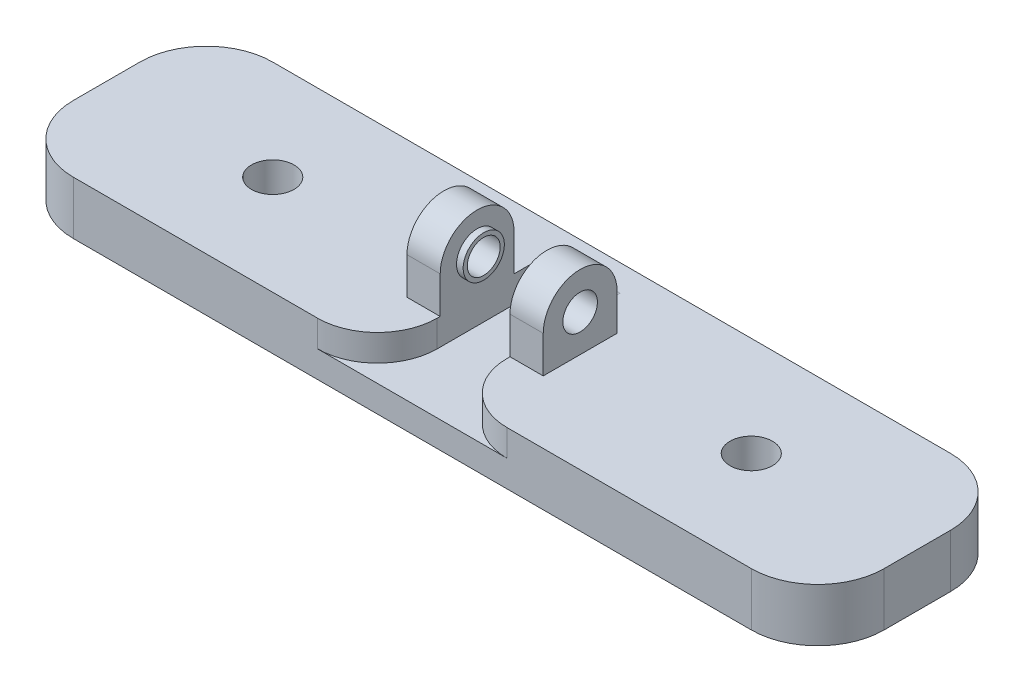
SolidWorks part; units mm, degrees
ref_plane "Front Plane" through (0, 0, 0) normal (0, 0, 1) x (1, 0, 0)
ref_plane "Top Plane" through (0, 0, 0) normal (0, 1, 0) x (1, 0, 0)
ref_plane "Right Plane" through (0, 0, 0) normal (1, 0, 0) x (0, 0, -1)
sketch "Sketch1" plane through (0, 0, 0) normal (0, 1, 0) x (1, 0, 0)
  line L1 (-61, 15) -> (61, 15)
  line L2 (-61, 15) -> (-61, -15)
  line L3 (-61, -15) -> (61, -15)
  line L4 (61, 15) -> (61, -15)
  line L5 (-61, 15) -> (61, -15) construction
  line L6 (-61, -15) -> (61, 15) construction
  point P0 (0, 0)
  dimension "D1" = 122
  dimension "D2" = 30
extrude "Boss-Extrude1" add sketch "Sketch1" along normal blind 8
ref_plane "Plane1" through (0, 0, 0) normal (1, 0, 0) x (0, 0, -1)
ref_plane "Plane2" through (5.25, 0, 0) normal (1, 0, 0) x (0, 0, -1)
ref_plane "Plane3" through (-5.25, 0, 0) normal (1, 0, 0) x (0, 0, -1)
sketch "Sketch2" plane through (5.25, 0, 0) normal (1, 0, 0) x (0, 0, -1)
  line L0 (0, 8) -> (0, 13.5522) construction
  line L1 (-15, 8) -> (15, 8) construction
  line L2 (-5.5522, 13.5522) -> (-5.5522, 8)
  line L3 (-5.5522, 8) -> (5.5522, 8)
  line L4 (5.5522, 8) -> (5.5522, 13.5522)
  circle A0 centre (0, 13.5522) radius 2.6
  arc A1 (5.5522, 13.5522) -> (-5.5522, 13.5522) centre (0, 13.5522) ccw
  dimension "D1" = 5.5522
  dimension "D2" = 5.2
  dimension "D3" = 5.5522
extrude "Boss-Extrude2" add sketch "Sketch2" along normal blind 5
sketch "Sketch3" plane through (-5.25, 0, 0) normal (1, 0, 0) x (0, 0, -1)
  line L0 (-5.5522, 13.5522) -> (-5.5522, 8)
  line L1 (-15, 8) -> (15, 8) construction
  line L2 (-5.5522, 8) -> (5.5522, 8) construction
  line L3 (-5.5522, 8) -> (5.5522, 8)
  line L4 (5.5522, 8) -> (5.5522, 13.5522)
  circle A0 centre (0, 13.5522) radius 2.475
  arc A1 (5.5522, 13.5522) -> (-5.5522, 13.5522) centre (0, 13.5522) ccw
  dimension "D1" = 4.95
extrude "Boss-Extrude3" add sketch "Sketch3" against normal blind 5
sketch "Sketch4" plane through (0, 8, 0) normal (0, 1, 0) x (1, 0, 0)
  line L0 (-61, -15) -> (61, -15) construction
  line L1 (-5.25, 9) -> (5.25, 9)
  line L2 (-5.25, 9) -> (-5.25, -15)
  line L3 (-5.25, -15) -> (5.25, -15)
  line L4 (5.25, 9) -> (5.25, -15)
  point P0 (-5.25, 5.5522)
  point P1 (5.25, -5.5522)
  point P8 (-4.25, 5.3855)
  point P9 (0, 0)
  point P10 (4.25, -15)
  point P13 (0, 0)
  dimension "D1" = 24
extrude "Cut-Extrude1" cut sketch "Sketch4" against normal blind 4
sketch "Sketch6" plane through (5.25, 0, 0) normal (-1, 0, 0) x (0, 0, 1)
  circle A0 centre (0, 13.5522) radius 2.6
  circle A1 centre (0, 13.5522) radius 3.1
  dimension "D1" = 5.2
  dimension "D2" = 6.2
extrude "Boss-Extrude4" add sketch "Sketch6" along normal blind 1
fillet "Fillet1" radius 10 4 edges at (-61, 4, -15) (-61, 4, 15) (61, 4, -15) (61, 4, 15)
sketch "Sketch7" plane through (0, 8, 0) normal (0, 1, 0) x (1, 0, 0)
  line L0 (-61, 5) -> (-61, -5) construction
  line L1 (0, 0) -> (0, 29.2953) construction
  circle A0 centre (-36, 0) radius 3.2
  circle A1 centre (36, 0) radius 3.2
  point P2 (-61, 0)
  dimension "D1" = 6.4
  dimension "D2" = 25
extrude "Cut-Extrude2" cut sketch "Sketch7" against normal through all
sketch "Sketch8" plane through (-5.25, 0, 0) normal (1, 0, 0) x (0, 0, -1)
  circle A0 centre (0, 13.5522) radius 2.475
  circle A1 centre (0, 13.5522) radius 3.1
  dimension "D1" = 4.95
  dimension "D2" = 6.2
extrude "Boss-Extrude5" add sketch "Sketch8" along normal blind 1
fillet "Fillet2" radius 9 2 edges at (5.25, 6, 15) (-5.25, 6, 15)
fillet "Fillet3" radius 2 1 edges at (0, 8, -9)
